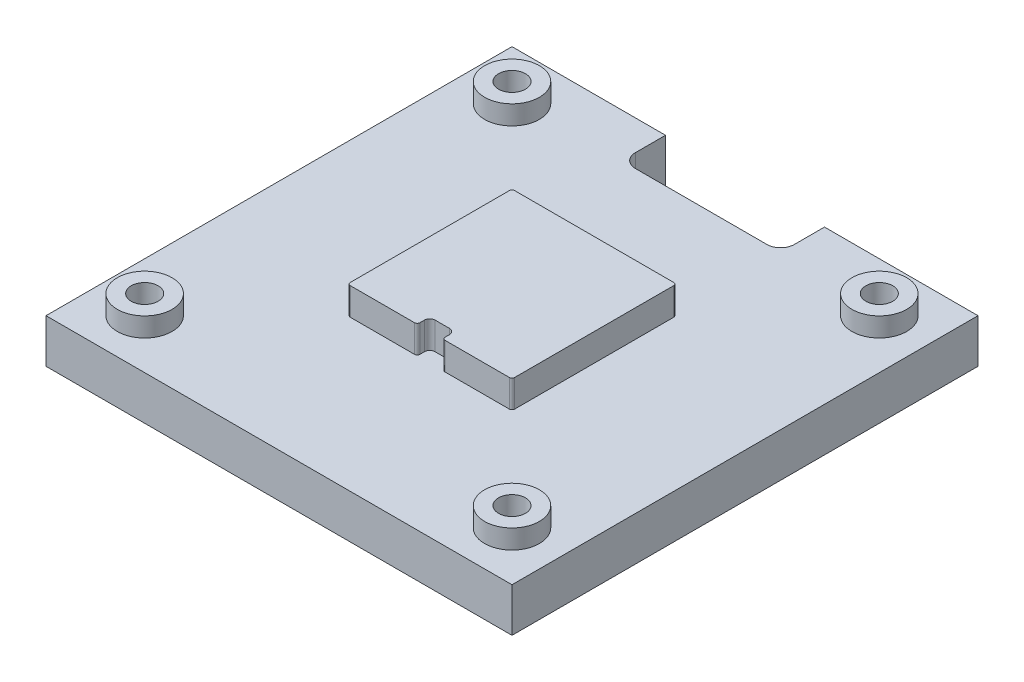
SolidWorks part; units mm, degrees
ref_plane "Front Plane" through (0, 0, 0) normal (0, 0, 1) x (1, 0, 0)
ref_plane "Top Plane" through (0, 0, 0) normal (0, 1, 0) x (1, 0, 0)
ref_plane "Right Plane" through (0, 0, 0) normal (1, 0, 0) x (0, 0, -1)
sketch "Sketch1" plane through (0, 0, 0) normal (0, 1, 0) x (1, 0, 0)
  line L0 (-71.3469, 0) -> (71.3469, 0) construction
  line L1 (-42.5, 42.5) -> (42.5, 42.5)
  line L2 (-42.5, 42.5) -> (-42.5, -42.5)
  line L3 (-42.5, -42.5) -> (42.5, -42.5)
  line L4 (42.5, 42.5) -> (42.5, -42.5)
  line L5 (-42.5, 42.5) -> (42.5, -42.5) construction
  line L6 (-42.5, -42.5) -> (42.5, 42.5) construction
  line L7 (0, -59.0713) -> (0, 59.0713) construction
  circle A0 centre (-33.5, 33.5) radius 2.4575
  circle A1 centre (-33.5, -33.5) radius 2.4575
  circle A2 centre (33.5, -33.5) radius 2.4575
  circle A3 centre (33.5, 33.5) radius 2.4575
  point P0 (0, 0)
  dimension "D3" = 4.915
  dimension "D1" = 85
  dimension "D2" = 85
  dimension "D4" = 9
  dimension "D5" = 9
extrude "Boss-Extrude1" add sketch "Sketch1" along normal blind 8
sketch "Sketch2" plane through (0, 0, 0) normal (0, -1, 0) x (1, 0, 0)
  line L0 (0, -4.4) -> (0, 4.4) construction
  line L1 (4.4, 0) -> (-4.4, 0) construction
  circle A0 centre (-33.5, 33.5) radius 3.969
  circle A1 centre (33.5, 33.5) radius 3.969
  circle A2 centre (33.5, -33.5) radius 3.969
  circle A3 centre (-33.5, -33.5) radius 3.969
  dimension "D1" = 7.938
extrude "Cut-Extrude1" cut sketch "Sketch2" against normal blind 4.166
sketch "Sketch3" plane through (0, 8, 0) normal (0, 1, 0) x (1, 0, 0)
  line L0 (0, -4.4) -> (0, 4.4) construction
  line L1 (-4.4, 0) -> (4.4, 0) construction
  circle A0 centre (33.5, -33.5) radius 5
  circle A1 centre (33.5, -33.5) radius 2.4575
  circle A2 centre (33.5, -33.5) radius 2.4575 construction
  circle A3 centre (-33.5, -33.5) radius 2.4575
  circle A4 centre (-33.5, -33.5) radius 5
  circle A5 centre (-33.5, 33.5) radius 5
  circle A6 centre (-33.5, 33.5) radius 2.4575
  circle A7 centre (33.5, 33.5) radius 2.4575
  circle A8 centre (33.5, 33.5) radius 5
  dimension "D1" = 10
extrude "Boss-Extrude2" add sketch "Sketch3" along normal blind 3.5
sketch "Sketch4" plane through (0, 8, 0) normal (0, 1, 0) x (1, 0, 0)
  line L0 (2.2929, -14.5) -> (2.2929, -13.7071)
  line L1 (14.5, -15) -> (2.7929, -15)
  line L2 (15, -14.5) -> (15, 14.5)
  line L3 (14.5, 15) -> (-14.5, 15)
  line L4 (-15, -14.5) -> (-15, 14.5)
  line L5 (15, -15) -> (-15, 15) construction
  line L6 (15, 15) -> (-15, -15) construction
  line L7 (1.2929, -12.7071) -> (-1.2929, -12.7071)
  line L8 (-2.2929, -13.7071) -> (-2.2929, -14.5)
  line L9 (-2.7929, -15) -> (-14.5, -15)
  arc A0 (-14.5, 15) -> (-15, 14.5) centre (-14.5, 14.5) ccw
  arc A1 (15, 14.5) -> (14.5, 15) centre (14.5, 14.5) ccw
  arc A2 (-14.5, -15) -> (-15, -14.5) centre (-14.5, -14.5) cw
  arc A3 (14.5, -15) -> (15, -14.5) centre (14.5, -14.5) ccw
  arc A4 (-2.2929, -14.5) -> (-2.7929, -15) centre (-2.7929, -14.5) cw
  arc A5 (2.2929, -14.5) -> (2.7929, -15) centre (2.7929, -14.5) ccw
  arc A6 (-1.2929, -12.7071) -> (-2.2929, -13.7071) centre (-1.2929, -13.7071) ccw
  arc A7 (2.2929, -13.7071) -> (1.2929, -12.7071) centre (1.2929, -13.7071) ccw
  point P0 (0, 0)
  point P10 (0, -12.7071)
  point P25 (-2.2929, -15)
  point P30 (-2.2929, -12.7071)
  point P33 (2.2929, -12.7071)
  dimension "D4" = 0.5
  dimension "D6" = 0.5
  dimension "D7" = 1
  dimension "D1" = 30
  dimension "D2" = 2.2929
  dimension "D3" = 4.5858
  dimension "D5" = 30
extrude "Boss-Extrude3" add sketch "Sketch4" along normal blind 5
sketch "Sketch5" plane through (0, 8, 0) normal (0, 1, 0) x (1, 0, 0)
  line L0 (42.5, 42.5) -> (-42.5, 42.5) construction
  line L1 (14.5, 42.5) -> (-14.5, 42.5)
  line L2 (14.5, 42.5) -> (14.5, 34.5)
  line L3 (14.5, 34.5) -> (-14.5, 34.5)
  line L4 (-14.5, 42.5) -> (-14.5, 34.5)
  point P6 (0, 34.5)
  dimension "D1" = 29
  dimension "D2" = 8
extrude "Cut-Extrude2" cut sketch "Sketch5" against normal blind 10
fillet "Fillet1" radius 2.5 2 edges at (-14.5, 4, -34.5) (14.5, 4, -34.5)
